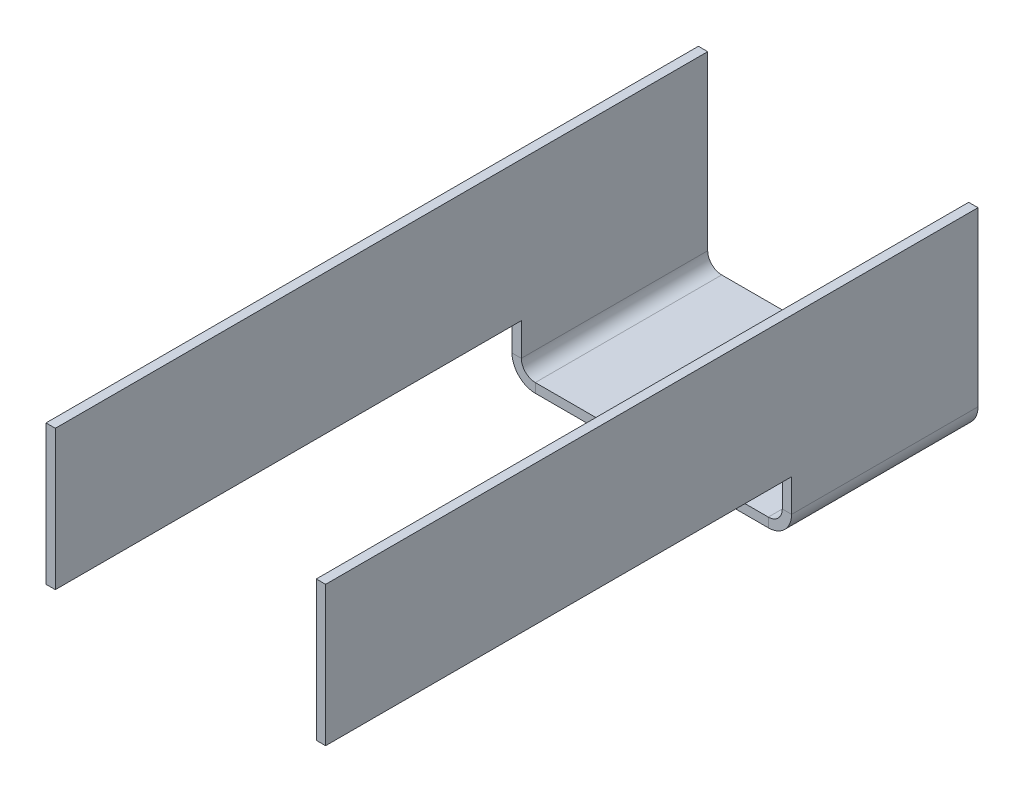
SolidWorks part; units mm, degrees
note: The reader was unsure of these and kept them because the rebuilt part matched: flange length of "Edge-Flange1", "Edge-Flange2".
ref_plane "Front Plane" through (0, 0, 0) normal (0, 0, 1) x (1, 0, 0)
ref_plane "Top Plane" through (0, 0, 0) normal (0, 1, 0) x (1, 0, 0)
ref_plane "Right Plane" through (0, 0, 0) normal (1, 0, 0) x (0, 0, -1)
sketch "Sketch1" plane through (0, 0, 0) normal (0, 1, 0) x (1, 0, 0)
  line L1 (-12.5, 10) -> (12.5, 10)
  line L2 (-12.5, 10) -> (-12.5, -10)
  line L3 (-12.5, -10) -> (12.5, -10)
  line L4 (12.5, 10) -> (12.5, -10)
  line L5 (-12.5, 10) -> (12.5, -10) construction
  line L6 (-12.5, -10) -> (12.5, 10) construction
  point P0 (0, 0)
  dimension "D1" = 25
  dimension "D2" = 20
base flange "Base-Flange1" sketch "Sketch1" thickness 1 reverse thickness direction no parameters "D1"=1.5
edge flange "Edge-Flange1" sketch "Sketch11" flange angle 90 flange length 20 flange position bend outside bend radius 1.5 thickness 1 relief rectangular parameters "D6"=10
sketch "Sketch11" plane through (-12.5, 0, 0) normal (-1, 0, 0) x (0, 0, 1)
  line L2 (-10, 0) -> (-10, 20)
  line L3 (-10, 20) -> (10, 20)
  line L4 (10, 20) -> (10, 0)
  line L5 (-10, 0) -> (10, 0) construction
  line L6 (-10, 0) -> (10, 0)
bend "EdgeBend1" bend radius 1.5 bend angle 90 parameters "D5"=1
edge flange "Edge-Flange2" sketch "Sketch14" flange angle 90 flange length 20 flange position bend outside bend radius 1.5 thickness 1 relief rectangular parameters "D6"=10
sketch "Sketch14" plane through (12.5, 0, 0) normal (1, 0, 0) x (0, 0, -1)
  line L0 (-10, 0) -> (10, 0) construction
  line L1 (-10, 0) -> (10, 0)
  line L2 (-10, 0) -> (-10, 20)
  line L3 (-10, 20) -> (10, 20)
  line L4 (10, 20) -> (10, 0)
bend "EdgeBend2" bend radius 1.5 bend angle 90 parameters "D5"=2
sketch "Sketch15" plane through (-14, 0, 0) normal (1, 0, 0) x (0, 0, -1)
  line L1 (-10, 20) -> (-60, 20)
  line L2 (-10, 20) -> (-10, 5)
  line L3 (-10, 5) -> (-60, 5)
  line L4 (-60, 20) -> (-60, 5)
  dimension "D1" = 50
  dimension "D2" = 15
base flange "Tab1" sketch "Sketch15" thickness 1 reverse thickness direction no parameters "D1"=1.5
sketch "Sketch18" plane through (15, 0, 0) normal (1, 0, 0) x (0, 0, -1)
  line L1 (-10, 20) -> (-60, 20)
  line L2 (-10, 20) -> (-10, 5)
  line L3 (-10, 5) -> (-60, 5)
  line L4 (-60, 20) -> (-60, 5)
  dimension "D1" = 15
  dimension "D2" = 50
base flange "Tab2" sketch "Sketch18" thickness 1 reverse thickness direction no parameters "D1"=1.5
sketch "Bend-Lines1" [suppressed] plane through (0, 0, 0) normal (0, 1, 0) x (1, 0, 0)
sketch "Bounding-Box1" [suppressed] plane through (0, 0, 0) normal (0, 1, 0) x (1, 0, 0)
sheet metal parameters "Sheet-Metal1" thickness 1 parameters "D1"=1.5
flat pattern "Flat-Pattern1" [suppressed]
sketch "Bend-Lines2" plane through (0, 0, 0) normal (0, 1, 0) x (1, 0, 0)
sketch3d "Bounding-Box2" [suppressed]
  line L0 (-12.5, -10, 0) -> (12.5, -10, 0) construction
  line L1 (-12.5, 10, 0) -> (12.5, 10, 0) construction
  line L2 (-12.5, -10, 0) -> (-12.5, 10, 0) construction
  line L3 (12.5, -10, 0) -> (12.5, 10, 0) construction
sheet metal parameters "Sheet-Metal2" thickness 1 parameters "D1"=1.5
flat pattern "Flat-Pattern1"
sketch "Bend-Lines2" plane through (0, 0, 0) normal (0, 1, 0) x (1, 0, 0)
  line L0 (-14.0708, 10) -> (-14.0708, -10) construction
  line L1 (-14.0708, 10) -> (-14.0708, -10) construction
sketch3d "Bounding-Box2" [suppressed]
  line L0 (12.5, -10, 0) -> (-34.1416, -10, 0) construction
  line L1 (12.5, 10, 0) -> (-34.1416, 10, 0) construction
  line L2 (12.5, -10, 0) -> (12.5, 10, 0) construction
  line L3 (-34.1416, -10, 0) -> (-34.1416, 10, 0) construction
bend of the flat pattern "Flatten-<EdgeBend1>1"
sheet metal parameters "Sheet-Metal3" thickness 1 parameters "D1"=1.5
flat pattern "Flat-Pattern1"
sketch "Bend-Lines2" plane through (0, 0, 0) normal (0, 1, 0) x (1, 0, 0)
  line L0 (-14.0708, 10) -> (-14.0708, -10) construction
  line L1 (-14.0708, 10) -> (-14.0708, -10) construction
  line L2 (14.0708, -10) -> (14.0708, 10) construction
  line L3 (14.0708, -10) -> (14.0708, 10) construction
sketch3d "Bounding-Box2" [suppressed]
  line L0 (34.1416, -10, 0) -> (-34.1416, -10, 0) construction
  line L1 (34.1416, 10, 0) -> (-34.1416, 10, 0) construction
  line L2 (34.1416, -10, 0) -> (34.1416, 10, 0) construction
  line L3 (-34.1416, -10, 0) -> (-34.1416, 10, 0) construction
bend of the flat pattern "Flatten-<EdgeBend1>1"
bend of the flat pattern "Flatten-<EdgeBend2>1"
sheet metal parameters "Sheet-Metal4" thickness 1 parameters "D1"=1.5
flat pattern "Flat-Pattern4"
sketch "Bend-Lines3" plane through (0, 0, 0) normal (0, 1, 0) x (1, 0, 0)
  line L0 (14.0708, -10) -> (14.0708, 10) construction
  line L1 (-14.0708, 10) -> (-14.0708, -10) construction
  line L2 (14.0708, -10) -> (14.0708, 10) construction
  line L3 (-14.0708, 10) -> (-14.0708, -10) construction
sketch3d "Bounding-Box3" [suppressed]
  line L0 (34.1416, -34.7283, 0) -> (-34.1416, -34.7283, 0) construction
  line L1 (34.1416, 10, 0) -> (-34.1416, 10, 0) construction
  line L2 (34.1416, -34.7283, 0) -> (34.1416, 10, 0) construction
  line L3 (-34.1416, -34.7283, 0) -> (-34.1416, 10, 0) construction
bend of the flat pattern "Flatten-<EdgeBend2>2"
bend of the flat pattern "Flatten-<EdgeBend1>2"
sheet metal parameters "Sheet-Metal5" thickness 1 parameters "D1"=1.5
flat pattern "Flat-Pattern5"
sketch "Bend-Lines4" plane through (0, 0, 0) normal (0, 1, 0) x (1, 0, 0)
  line L0 (14.0708, -10) -> (14.0708, 10) construction
  line L1 (-14.0708, 10) -> (-14.0708, -10) construction
  line L2 (14.0708, -10) -> (14.0708, 10) construction
  line L3 (-14.0708, 10) -> (-14.0708, -10) construction
sketch3d "Bounding-Box4" [suppressed]
  line L0 (-34.1416, 10, 0) -> (-34.1416, -60, 0) construction
  line L1 (34.1416, 10, 0) -> (34.1416, -60, 0) construction
  line L2 (-34.1416, 10, 0) -> (34.1416, 10, 0) construction
  line L3 (-34.1416, -60, 0) -> (34.1416, -60, 0) construction
bend of the flat pattern "Flatten-<EdgeBend2>3"
bend of the flat pattern "Flatten-<EdgeBend1>3"
